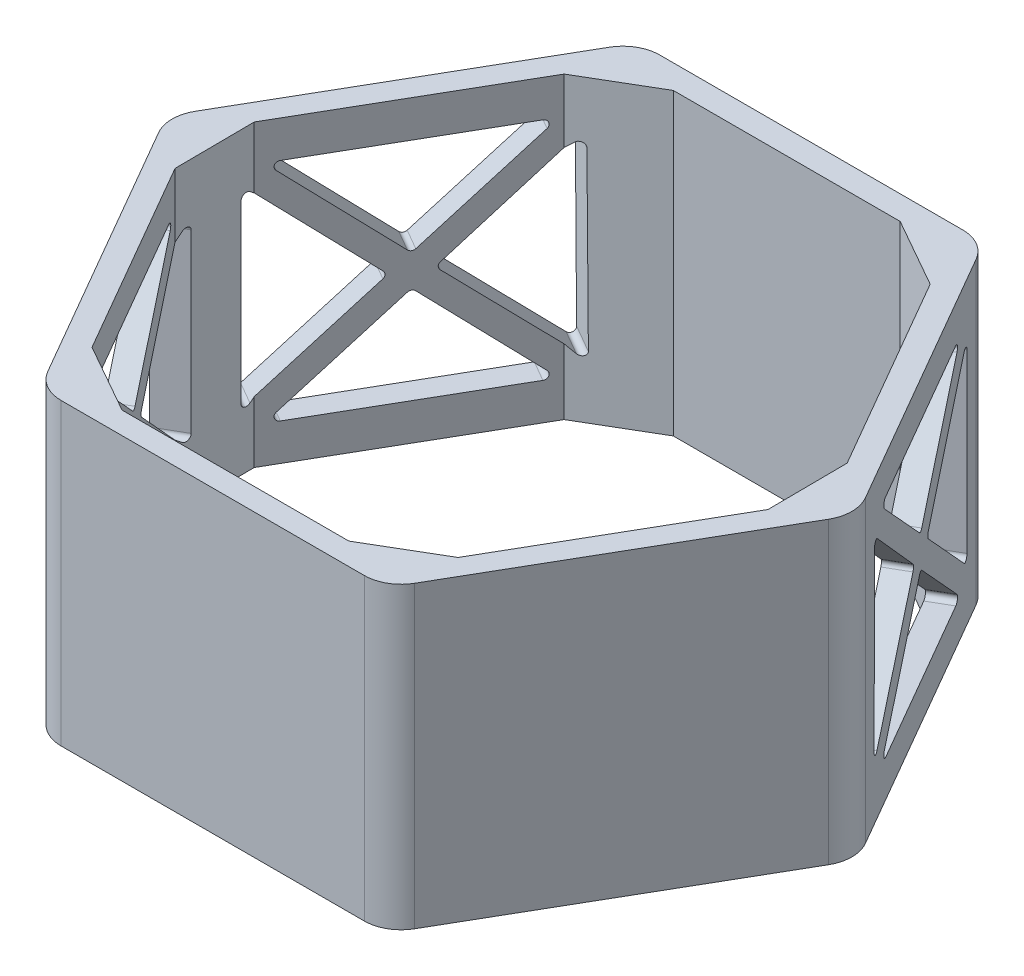
SolidWorks part; units mm, degrees
other "Markup1"
sketch "Sketch3" plane through (-73.8179, 60, -65.1972) normal (0, 1, 0) x (1, 0, 0)
ref_plane "Front Plane" through (0, 0, 0) normal (0, 0, 1) x (1, 0, 0)
ref_plane "Top Plane" through (0, 0, 0) normal (0, 1, 0) x (1, 0, 0)
ref_plane "Right Plane" through (0, 0, 0) normal (1, 0, 0) x (0, 0, -1)
sketch "Sketch1" plane through (0, 0, 0) normal (0, 1, 0) x (1, 0, 0)
  line L0 (-75.0555, 0.1972) -> (-37.5278, -64.8028)
  line L1 (-37.5278, -64.8028) -> (37.5278, -64.8028)
  line L2 (37.5278, -64.8028) -> (75.0555, 0.1972)
  line L3 (75.0555, 0.1972) -> (37.5278, 65.1972)
  line L4 (37.5278, 65.1972) -> (-37.5278, 65.1972)
  line L5 (-37.5278, 65.1972) -> (-75.0555, 0.1972)
  line L6 (-55.8021, -33.1507) -> (56.2917, 32.6972) construction
  line L7 (0.0854, 0.0493) -> (-56.2917, 32.6972) construction
  circle A0 centre (0.0854, 0.0493) radius 65 construction
  circle A1 centre (0.0854, 0.0493) radius 50 construction
  dimension "D1" = 100
  dimension "D2" = 130
extrude "Boss-Extrude1" add sketch "Sketch1" along normal blind 65
fillet "Fillet1" radius 8 6 edges at (-37.5278, 32.5, -65.1972) (-75.0555, 32.5, -0.1972) (-37.5278, 32.5, 64.8028) (37.5278, 32.5, 64.8028) (75.0555, 32.5, -0.1972) (37.5278, 32.5, -65.1972)
sketch "Sketch2" plane through (0, 0, 0) normal (0, 1, 0) x (1, 0, 0)
  line L0 (-39.7072, 51.225) -> (-24.7695, 60)
  line L1 (64.2158, 8.775) -> (39.5768, 51.451)
  line L2 (24.5086, 60) -> (-24.7695, 60)
  line L3 (-39.7072, 51.225) -> (-64.3463, 8.549)
  line L4 (-64.2158, -8.775) -> (-39.5768, -51.451)
  line L5 (-24.5086, -60) -> (24.7695, -60)
  line L6 (39.7072, -51.225) -> (64.3463, -8.549)
  line L7 (75.0555, 0.1972) -> (37.5278, 65.1972) construction
  line L8 (-55.8021, -33.1507) -> (56.2917, 32.6972) construction
  line L9 (24.5086, 60) -> (39.5768, 51.451)
  line L10 (64.2158, 8.775) -> (64.3463, -8.549)
  line L11 (39.7072, -51.225) -> (24.7695, -60)
  line L12 (-24.5086, -60) -> (-39.5768, -51.451)
  line L13 (-64.2158, -8.775) -> (-64.3463, 8.549)
  line L14 (-34.641, 60) -> (-39.7072, 51.225) construction
  line L15 (-24.7695, 60) -> (-34.641, 60) construction
  line L16 (34.641, 60) -> (24.5086, 60) construction
  line L17 (39.5768, 51.451) -> (34.641, 60) construction
  line L18 (69.282, 0) -> (64.2158, 8.775) construction
  line L19 (64.3463, -8.549) -> (69.282, 0) construction
  line L20 (34.641, -60) -> (39.7072, -51.225) construction
  line L21 (24.7695, -60) -> (34.641, -60) construction
  line L22 (-34.641, -60) -> (-24.5086, -60) construction
  line L23 (-39.5768, -51.451) -> (-34.641, -60) construction
  line L24 (-64.3463, 8.549) -> (-69.282, 0) construction
  line L25 (-69.282, 0) -> (-64.2158, -8.775) construction
  circle A0 centre (0, 0) radius 60 construction
  point P28 (0, 0)
  dimension "D1" = 120
  dimension "D2" = 5
  dimension "D3" = 6
extrude "Cut-Extrude1" cut sketch "Sketch2" along normal up to surface (65 mm away) up to face at (0, 65, -0.1972)
sketch "Sketch4" plane through (-56.2063, 0, 32.4507) normal (-0.866, 0, 0.5) x (0.5, 0, 0.866)
  line L0 (-0.1708, 65) -> (0, 0) construction
  line L1 (-33.0797, 65) -> (32.7382, 65) construction
  line L2 (-30.0854, 13.3588) -> (-30.0854, 51.6412) construction
  line L3 (29.9146, 59.5) -> (-30.0854, 59.5) construction
  line L4 (29.9146, 59.5) -> (29.9146, 5.5) construction
  line L5 (29.9146, 5.5) -> (-30.0854, 5.5) construction
  line L6 (-30.0854, 59.5) -> (-30.0854, 5.5) construction
  line L7 (29.9146, 59.5) -> (-30.0854, 5.5) construction
  line L8 (29.9146, 5.5) -> (-30.0854, 59.5) construction
  line L9 (-24.244, 54.2428) -> (-2.976, 35.1015) construction
  line L10 (-2.976, 29.8985) -> (-24.244, 10.7572) construction
  line L14 (-20.9645, 59.5) -> (20.7938, 59.5) construction
  line L15 (23.1351, 53.3985) -> (2.256, 34.6072) construction
  line L16 (-2.4268, 34.6072) -> (-23.3059, 53.3985) construction
  line L20 (-0.0854, 32.5) -> (15.0544, 32.5) construction
  line L27 (-4.6484, 31.7567) -> (-25.9164, 12.6155)
  line L28 (-27.5854, 13.3588) -> (-27.5854, 51.6412)
  line L29 (-25.9164, 52.3845) -> (-4.6484, 33.2433)
  line L30 (-0.7544, 36.4655) -> (-21.6335, 55.2567)
  line L31 (-20.9645, 57) -> (20.7938, 57)
  line L32 (21.4627, 55.2567) -> (0.5836, 36.4655)
  line L33 (21.4627, 9.7433) -> (0.5836, 28.5345)
  line L34 (-20.9645, 8) -> (20.7938, 8)
  line L35 (-0.7544, 28.5345) -> (-21.6335, 9.7433)
  line L36 (25.6408, 52.52) -> (4.4736, 33.2673)
  line L37 (27.5148, 13.5035) -> (27.3137, 51.7855)
  line L38 (4.4815, 31.7807) -> (25.8498, 12.7515)
  arc A0 (-24.244, 10.7572) -> (-30.0854, 13.3588) centre (-26.5854, 13.3588) cw construction
  arc A1 (-2.976, 29.8985) -> (-2.976, 35.1015) centre (-5.3174, 32.5) ccw construction
  arc A2 (-30.0854, 51.6412) -> (-24.244, 54.2428) centre (-26.5854, 51.6412) cw construction
  arc A6 (2.256, 34.6072) -> (-2.4268, 34.6072) centre (-0.0854, 37.2088) cw construction
  arc A7 (23.1351, 53.3985) -> (20.7938, 59.5) centre (20.7938, 56) ccw construction
  arc A8 (-20.9645, 59.5) -> (-23.3059, 53.3985) centre (-20.9645, 56) ccw construction
  arc A18 (-25.9164, 12.6155) -> (-27.5854, 13.3588) centre (-26.5854, 13.3588) cw
  arc A19 (-27.5854, 51.6412) -> (-25.9164, 52.3845) centre (-26.5854, 51.6412) cw
  arc A20 (-4.6484, 31.7567) -> (-4.6484, 33.2433) centre (-5.3174, 32.5) ccw
  arc A21 (-20.9645, 57) -> (-21.6335, 55.2567) centre (-20.9645, 56) ccw
  arc A22 (21.4627, 55.2567) -> (20.7938, 57) centre (20.7938, 56) ccw
  arc A23 (0.5836, 36.4655) -> (-0.7544, 36.4655) centre (-0.0854, 37.2088) cw
  arc A24 (0.5836, 28.5345) -> (-0.7544, 28.5345) centre (-0.0854, 27.7912) ccw
  arc A25 (21.4627, 9.7433) -> (20.7938, 8) centre (20.7938, 9) cw
  arc A26 (-20.9645, 8) -> (-21.6335, 9.7433) centre (-20.9645, 9) cw
  arc A27 (4.4815, 31.7807) -> (4.4736, 33.2673) centre (5.1465, 32.5275) cw
  arc A28 (27.3137, 51.7855) -> (25.6408, 52.52) centre (26.3137, 51.7802) ccw
  arc A29 (25.8498, 12.7515) -> (27.5148, 13.5035) centre (26.5148, 13.4983) ccw
  point P5 (-0.0854, 32.5)
  point P16 (-0.0854, 32.5)
  point P32 (-0.0854, 32.5)
  dimension "D3" = 3.5
  dimension "D4" = 3.5
  dimension "D1" = 60
  dimension "D2" = 54
  dimension "D5" = 2.5
  dimension "D6" = 2.5
extrude "Cut-Extrude2" cut sketch "Sketch4" against normal up to surface (130 mm away) up to face at (56.2917, 32.5, -32.6972)
sketch "Sketch6" plane through (-56.2063, 0, -32.8451) normal (0.866, 0, 0.5) x (0.5, 0, -0.866)
  line L0 (-0.1708, 65) -> (0, 0) construction
  line L2 (-30.0854, 13.3588) -> (-30.0854, 51.6412) construction
  line L3 (29.9146, 59.5) -> (-30.0854, 59.5) construction
  line L4 (29.9146, 59.5) -> (29.9146, 5.5) construction
  line L5 (29.9146, 5.5) -> (-30.0854, 5.5) construction
  line L6 (-30.0854, 59.5) -> (-30.0854, 5.5) construction
  line L7 (29.9146, 59.5) -> (-30.0854, 5.5) construction
  line L8 (29.9146, 5.5) -> (-30.0854, 59.5) construction
  line L9 (-24.244, 54.2428) -> (-2.976, 35.1015) construction
  line L10 (-2.976, 29.8985) -> (-24.244, 10.7572) construction
  line L14 (-20.9645, 59.5) -> (20.7938, 59.5) construction
  line L15 (23.1351, 53.3985) -> (2.256, 34.6072) construction
  line L16 (-2.4268, 34.6072) -> (-23.3059, 53.3985) construction
  line L20 (-0.0854, 32.5) -> (15.0544, 32.5) construction
  line L27 (-4.6484, 31.7567) -> (-25.9164, 12.6155)
  line L28 (-27.5854, 13.3588) -> (-27.5854, 51.6412)
  line L29 (-25.9164, 52.3845) -> (-4.6484, 33.2433)
  line L30 (-0.7544, 36.4655) -> (-21.6335, 55.2567)
  line L31 (-20.9645, 57) -> (20.7938, 57)
  line L32 (21.4627, 55.2567) -> (0.5836, 36.4655)
  line L33 (21.4627, 9.7433) -> (0.5836, 28.5345)
  line L34 (-20.9645, 8) -> (20.7938, 8)
  line L35 (-0.7544, 28.5345) -> (-21.6335, 9.7433)
  line L36 (25.6408, 52.52) -> (4.4736, 33.2673)
  line L37 (27.5148, 13.5035) -> (27.3137, 51.7855)
  line L38 (4.4815, 31.7807) -> (25.8498, 12.7515)
  arc A0 (-24.244, 10.7572) -> (-30.0854, 13.3588) centre (-26.5854, 13.3588) cw construction
  arc A1 (-2.976, 29.8985) -> (-2.976, 35.1015) centre (-5.3174, 32.5) ccw construction
  arc A2 (-30.0854, 51.6412) -> (-24.244, 54.2428) centre (-26.5854, 51.6412) cw construction
  arc A6 (2.256, 34.6072) -> (-2.4268, 34.6072) centre (-0.0854, 37.2088) cw construction
  arc A7 (23.1351, 53.3985) -> (20.7938, 59.5) centre (20.7938, 56) ccw construction
  arc A8 (-20.9645, 59.5) -> (-23.3059, 53.3985) centre (-20.9645, 56) ccw construction
  arc A18 (-25.9164, 12.6155) -> (-27.5854, 13.3588) centre (-26.5854, 13.3588) cw
  arc A19 (-27.5854, 51.6412) -> (-25.9164, 52.3845) centre (-26.5854, 51.6412) cw
  arc A20 (-4.6484, 31.7567) -> (-4.6484, 33.2433) centre (-5.3174, 32.5) ccw
  arc A21 (-20.9645, 57) -> (-21.6335, 55.2567) centre (-20.9645, 56) ccw
  arc A22 (21.4627, 55.2567) -> (20.7938, 57) centre (20.7938, 56) ccw
  arc A23 (0.5836, 36.4655) -> (-0.7544, 36.4655) centre (-0.0854, 37.2088) cw
  arc A24 (0.5836, 28.5345) -> (-0.7544, 28.5345) centre (-0.0854, 27.7912) ccw
  arc A25 (21.4627, 9.7433) -> (20.7938, 8) centre (20.7938, 9) cw
  arc A26 (-20.9645, 8) -> (-21.6335, 9.7433) centre (-20.9645, 9) cw
  arc A27 (4.4815, 31.7807) -> (4.4736, 33.2673) centre (5.1465, 32.5275) cw
  arc A28 (27.3137, 51.7855) -> (25.6408, 52.52) centre (26.3137, 51.7802) ccw
  arc A29 (25.8498, 12.7515) -> (27.5148, 13.5035) centre (26.5148, 13.4983) ccw
  point P5 (-0.0854, 32.5)
  point P16 (-0.0854, 32.5)
  point P32 (-0.0854, 32.5)
extrude "Cut-Extrude3" cut sketch "Sketch6" along normal blind 50
